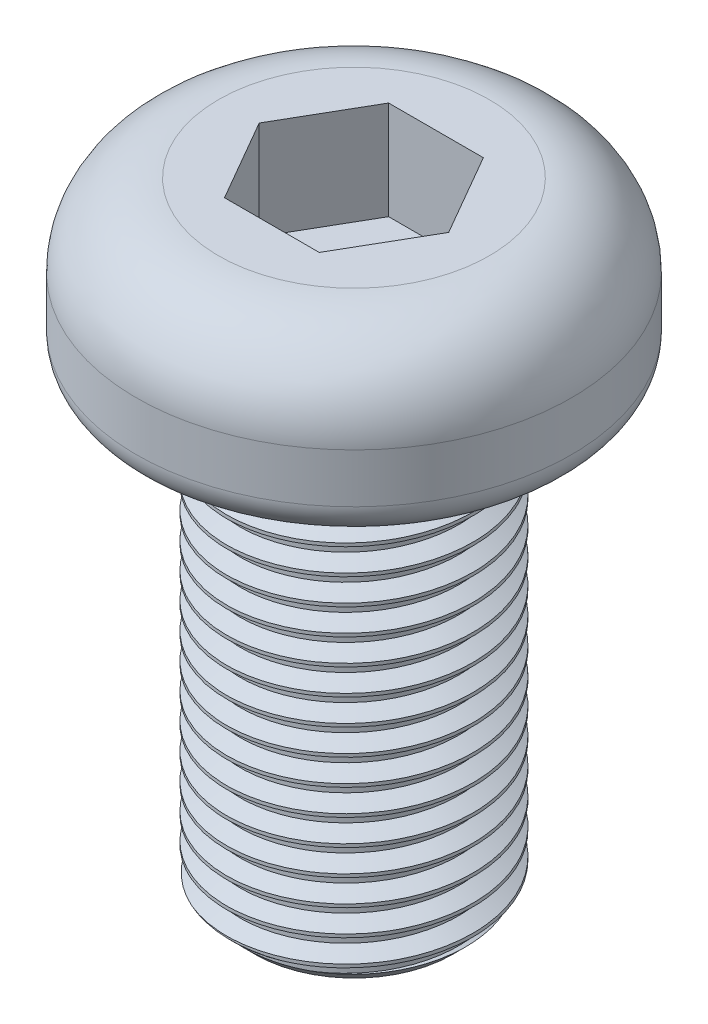
SolidWorks part; units mm, degrees
ref_plane "前视基准面" through (0, 0, 0) normal (0, 0, 1) x (1, 0, 0)
ref_plane "上视基准面" through (0, 0, 0) normal (0, 1, 0) x (1, 0, 0)
ref_plane "右视基准面" through (0, 0, 0) normal (1, 0, 0) x (0, 0, -1)
sketch "草图4" plane through (0, 0, 0) normal (0, 0, 1) x (1, 0, 0)
  line L0 (0, 0) -> (-1.5, 0)
  line L1 (-1.5, 0) -> (-1.5, 5.6)
  line L2 (-1.5, 5.6) -> (-2.25, 5.6)
  line L3 (-2.65, 6) -> (-2.65, 6.6)
  line L4 (-1.65, 7.6) -> (0, 7.6)
  line L5 (0, 7.6) -> (0, 0)
  arc A0 (-2.65, 6.6) -> (-1.65, 7.6) centre (-1.65, 6.6) cw
  arc A1 (-2.25, 5.6) -> (-2.65, 6) centre (-2.25, 6) cw
  point P9 (-13.1106, 5.1688)
  point P10 (-3.7941, 0)
  point P11 (-6.0042, 4.9988)
  dimension "D1" = 1
  dimension "D6" = 0.4
  dimension "D2" = 7.6
  dimension "D3" = 1.5
  dimension "D4" = 2.65
  dimension "D5" = 2
revolve "旋转1" add sketch "草图4" angle 360 about L5
sketch "草图5" plane through (0, 7.6, 0) normal (0, 1, 0) x (1, 0, 0)
  line L1 (0.5774, 1) -> (-0.5774, 1)
  line L2 (-0.5774, 1) -> (-1.1547, 0)
  line L3 (-1.1547, 0) -> (-0.5774, -1)
  line L4 (-0.5774, -1) -> (0.5774, -1)
  line L5 (0.5774, -1) -> (1.1547, 0)
  line L6 (1.1547, 0) -> (0.5774, 1)
  circle A0 centre (0, 0) radius 1 construction
  dimension "D1" = 2
extrude "切除-拉伸1" cut sketch "草图5" against normal blind 1.2
chamfer "倒角1" distance 0.3 angle 45 1 edges at (-1.5, 0, 0)
thread "螺纹线1" pitch 0.3175 method cut profile "螺纹线轮廓1" start angle 0, offset 0, length 0, pitch 0.3175, diameter 3
ref_plane "基准面1" through (-1.5, 5.6, 0) normal (0, 0, 1) x (-1, 0, 0)
sketch "螺纹线轮廓1" plane through (-1.5, 5.6, 0) normal (0, 0, 1) x (-1, 0, 0)
  line L0 (0, 0) -> (0, 0.3175) construction
  line L11 (0, 0) -> (0, 0.2778)
  line L12 (0, 0.2778) -> (-0.1719, 0.1786)
  line L13 (-0.1719, 0.1786) -> (-0.1719, 0.0992)
  line L15 (-0.1719, 0.0992) -> (0, 0)
  line L17 (-0.1719, 0.1389) -> (0, 0.1389) construction
  point P2 (0, 0)
  dimension "Pitch" = 0.3175
  dimension "Profile_Angle" = 60
  dimension "Profile_Land" = 0.0794
  dimension "Profile_Height" = 0.1719
